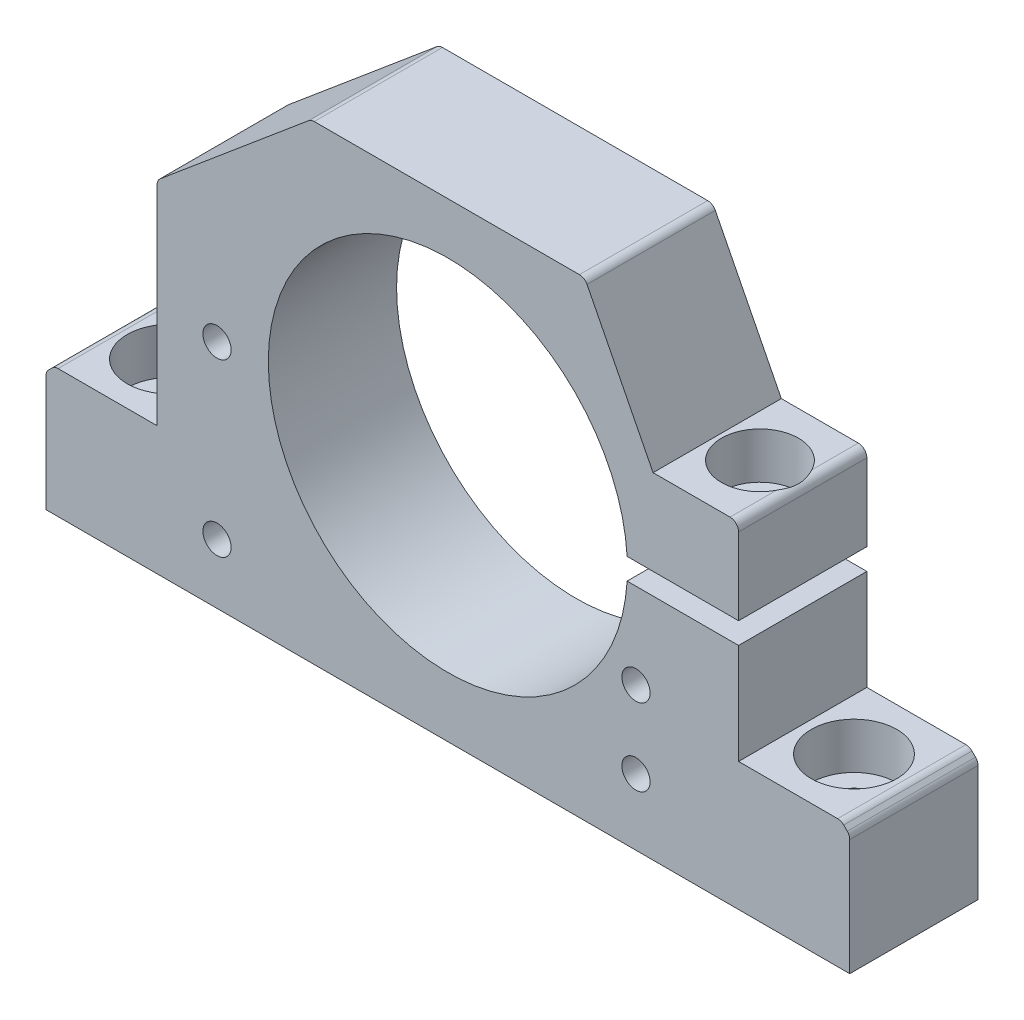
SolidWorks part; units mm, degrees
ref_plane "Front Plane" through (0, 0, 0) normal (0, 0, 1) x (1, 0, 0)
ref_plane "Top Plane" through (0, 0, 0) normal (0, 1, 0) x (1, 0, 0)
ref_plane "Right Plane" through (0, 0, 0) normal (1, 0, 0) x (0, 0, -1)
sketch "Sketch1" plane through (0, 0, 0) normal (0, 0, 1) x (1, 0, 0)
  line L0 (0, -36.6731) -> (0, 36.6731) construction
  line L1 (0, 0) -> (-62.0968, 0) construction
  line L2 (47, -28) -> (-47, -28)
  line L3 (-47, -28) -> (-47, -13)
  line L4 (-47, -13) -> (-34, -13)
  line L5 (-34, -13) -> (-34, 27)
  line L6 (-34, 27) -> (34, 27)
  line L7 (47, -28) -> (47, -13)
  line L8 (34, -13) -> (34, 27)
  line L9 (47, -13) -> (34, -13)
  circle A0 centre (0, 0) radius 21
  point P6 (0, 0)
  point P14 (0, 27)
  point P15 (0, -28)
  dimension "D1" = 42
  dimension "D2" = 47
  dimension "D3" = 15
  dimension "D4" = 40
  dimension "D5" = 28
  dimension "D6" = 34
extrude "Boss-Extrude1" add sketch "Sketch1" along normal blind 15
sketch "Sketch2" plane through (0, 0, 15) normal (0, 0, 1) x (1, 0, 0)
  line L0 (0, 0) -> (45.477, 0) construction
  line L1 (34, -13) -> (34, 27) construction
  line L2 (55.1006, -1.25) -> (12.8994, -1.25)
  line L3 (55.1006, -1.25) -> (55.1006, 1.25)
  line L4 (55.1006, 1.25) -> (12.8994, 1.25)
  line L5 (12.8994, -1.25) -> (12.8994, 1.25)
  line L6 (55.1006, -1.25) -> (12.8994, 1.25) construction
  line L7 (55.1006, 1.25) -> (12.8994, -1.25) construction
  point P3 (34, 0)
  dimension "D1" = 2.5
extrude "Cut-Extrude1" cut sketch "Sketch2" against normal blind 15
sketch "Sketch3" plane through (0, 0, 15) normal (0, 0, 1) x (1, 0, 0)
  line L0 (34, 27) -> (16, 27)
  line L1 (34, 27) -> (-34, 27) construction
  line L2 (16, 27) -> (24, 11.25)
  line L3 (34, 11.25) -> (34, 27)
  line L4 (34, 1.25) -> (34, 27) construction
  line L5 (24, 11.25) -> (34, 11.25)
  line L6 (34, 1.25) -> (20.9628, 1.25) construction
  dimension "D1" = 18
  dimension "D2" = 10
  dimension "D3" = 10
extrude "Cut-Extrude2" cut sketch "Sketch3" against normal blind 15
sketch "Sketch4" plane through (0, -13, 0) normal (0, 1, 0) x (1, 0, 0)
  line L0 (-47, -7.5) -> (47, -7.5) construction
  line L1 (-47, -15) -> (-47, 0) construction
  line L2 (47, -15) -> (47, 0) construction
  line L3 (0, 0) -> (0, -15) construction
  line L4 (16, -15) -> (-34, -15) construction
  circle A0 centre (-40, -7.5) radius 4
  circle A1 centre (40, -7.5) radius 4
  dimension "D2" = 8
  dimension "D1" = 40
hole_wizard "CBORE SLOT for M5 Hex Socket Head Cap Screw1" positions "Sketch5" profile "Sketch6" size "M5" standard "ISO" slot yes end condition through all
sketch "Sketch5" plane through (0, -13, 0) normal (0, 1, 0) x (1, 0, 0)
  point P0 (-40, -7.5)
  point P3 (40, -7.5)
sketch "Sketch6" plane through (-40, -13, 7.5) normal (1, 0, 0) x (0, 0, 1)
  line L0 (0, 0) -> (0, 15)
  line L1 (0, 15) -> (2.75, 15)
  line L3 (2.75, 15) -> (2.75, 5.4)
  line L4 (2.75, 5.4) -> (5, 5.4)
  line L5 (5, 5.4) -> (5, 0)
  line L7 (5, 0) -> (0, 0)
  line L11 (0, -6.35) -> (0, 107.95) construction
  dimension "Thru Hole Dia." = 5.5
  dimension "Thru Hole Depth" = 15
  dimension "C'Bore Dia." = 10
  dimension "C'Bore Depth" = 5.4
sketch "Sketch7" plane through (0, 11.25, 0) normal (0, 1, 0) x (1, 0, 0)
  line L0 (47, -7.5) -> (-47, -7.5) construction
  line L1 (47, -15) -> (47, 0) construction
  line L2 (-47, -15) -> (-47, 0) construction
  line L3 (34, 0) -> (34, -15) construction
  circle A0 centre (29, -7.5) radius 3.7072
  dimension "D1" = 5
hole_wizard "CBORE for M5 Hex Socket Head Cap Screw1" positions "3DSketch1" profile "Sketch8" counterbore size "M5" standard "ISO"
sketch3d "3DSketch1"
  point P0 (29, 11.25, 7.5)
sketch "Sketch8" plane through (29, 11.25, 7.5) normal (1, 0, 0) x (0, 0, 1)
  line L0 (0, 0) -> (0, 10)
  line L1 (0, 10) -> (2.75, 10)
  line L3 (2.75, 10) -> (2.75, 5.4)
  line L4 (2.75, 5.4) -> (4.5, 5.4)
  line L5 (4.5, 5.4) -> (4.5, 0)
  line L7 (4.5, 0) -> (0, 0)
  line L11 (0, -6.35) -> (0, 107.95) construction
  dimension "Thru Hole Dia." = 5.5
  dimension "Thru Hole Depth" = 10
  dimension "C'Bore Dia." = 9
  dimension "C'Bore Depth" = 5.4
chamfer "Chamfer1" distance 1 angle 45 2 edges at (47, -13, 7.5) (-47, -13, 7.5)
sketch "Sketch9" plane through (0, 0, 15) normal (0, 0, 1) x (1, 0, 0)
  line L0 (-27, -1) -> (-27, -21) construction
  line L1 (-47, -28) -> (47, -28) construction
  line L2 (-34, 27) -> (-34, -13) construction
  line L3 (22, -11.25) -> (22, -20.2587) construction
  line L4 (20.9628, -1.25) -> (34, -1.25) construction
  line L5 (34, -13) -> (34, -1.25) construction
  circle A0 centre (-27, -1) radius 2.3306
  circle A1 centre (-27, -21) radius 2.3306
  circle A2 centre (22, -11.25) radius 2.3306
  circle A3 centre (22, -20.2587) radius 2.3306
  dimension "D1" = 7
  dimension "D2" = 7
  dimension "D3" = 20
  dimension "D4" = 10
  dimension "D5" = 12
hole_wizard "M4 Tapped Hole1" positions "3DSketch2" profile "Sketch10" tap size "M4" standard "GB" end condition through all
sketch3d "3DSketch2"
  point P0 (-27, -21, 15)
  point P3 (-27, -1, 15)
  point P6 (22, -20.2587, 15)
  point P9 (22, -11.25, 15)
cosmetic thread "Hole Thread1" parameters "D2"=4
cosmetic thread "Hole Thread2" parameters "D2"=4
cosmetic thread "Hole Thread3" parameters "D2"=4
cosmetic thread "Hole Thread4" parameters "D2"=4
sketch "Sketch10" plane through (-27, -21, 15) normal (1, 0, 0) x (0, -1, 0)
  line L0 (0, 0) -> (0, 15)
  line L1 (0, 15) -> (1.65, 15)
  line L2 (1.65, 15) -> (1.65, 0)
  line L5 (1.65, 0) -> (0, 0)
  line L11 (0, -6.35) -> (0, 107.95) construction
  dimension "Thru Tap Drill Dia." = 3.3
  dimension "Thru Tap Drill Depth" = 15
sketch "Sketch11" plane through (0, -1.25, 0) normal (0, 1, 0) x (1, 0, 0)
  circle A0 centre (29, -7.5) radius 1.2081
hole_wizard "M5 Tapped Hole1" positions "3DSketch3" profile "Sketch12" tap size "M5" standard "GB"
sketch3d "3DSketch3"
  point P0 (29, -1.25, 7.5)
sketch "Sketch12" plane through (29, -1.25, 7.5) normal (1, 0, 0) x (0, 0, 1)
  line L0 (0, 0) -> (0, 19.2618)
  line L1 (0, 19.2618) -> (2.1, 18)
  line L2 (2.1, 18) -> (2.1, 0)
  line L5 (2.1, 0) -> (0, 0)
  line L10 (0, 19.2618) -> (-2.1, 18) construction
  line L11 (0, -6.35) -> (0, 107.95) construction
  dimension "Tap Drill Dia." = 4.2
  dimension "Tap Drill Depth" = 18
  dimension "Drill Angle" = 118
cosmetic thread "Hole Thread5" parameters "D1"=14, "D2"=5
chamfer "Chamfer2" distance 18 angle 40 1 edges at (-34, 27, 7.5)
fillet "Fillet1" radius 1 8 edges at (34, 11.25, 7.5) (46, -13, 7.5) (47, -14, 7.5) (16, 27, 7.5) (-16, 27, 7.5) (-34, 11.8962, 7.5) (-46, -13, 7.5) (-47, -14, 7.5)
